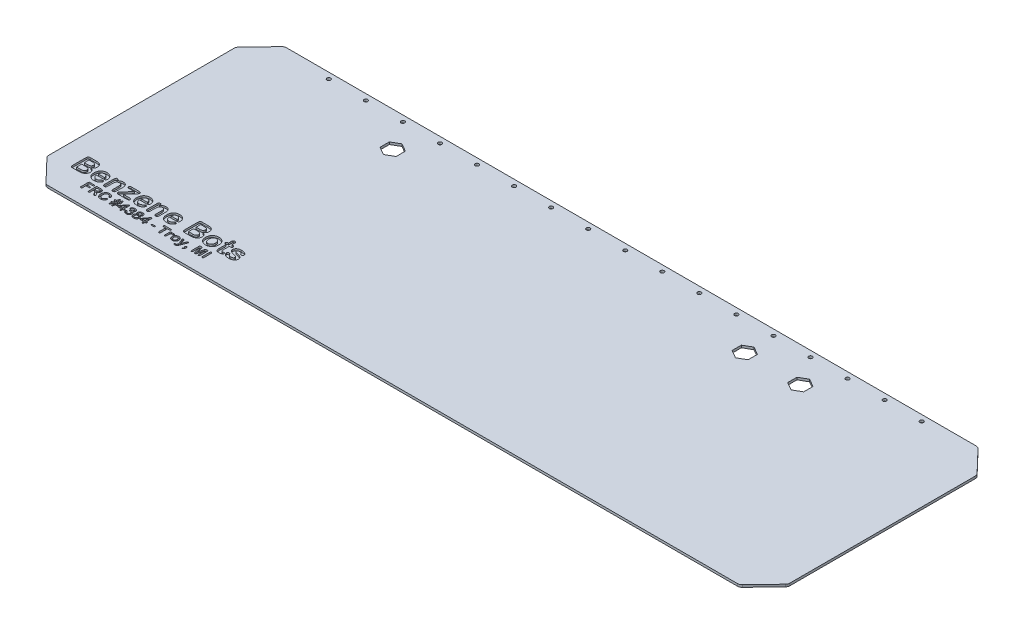
SolidWorks part; units mm, degrees
ref_plane "Front" through (0, 0, 0) normal (0, 0, 1) x (1, 0, 0)
ref_plane "Top" through (0, 0, 0) normal (0, 1, 0) x (1, 0, 0)
ref_plane "Right" through (0, 0, 0) normal (1, 0, 0) x (0, 0, -1)
sketch "Sketch1" plane through (0, 0, 0) normal (0, 1, 0) x (1, 0, 0)
  line L1 (6.35, 0) -> (1009.65, 0)
  line L2 (0, 6.35) -> (0, 320.675)
  line L3 (6.35, 327.025) -> (1009.65, 327.025)
  line L4 (1016, 6.35) -> (1016, 320.675)
  line L5 (0, 0) -> (1016, 327.025) construction
  line L6 (0, 327.025) -> (1016, 0) construction
  arc A0 (1009.65, 327.025) -> (1016, 320.675) centre (1009.65, 320.675) cw
  arc A1 (1009.65, 0) -> (1016, 6.35) centre (1009.65, 6.35) ccw
  arc A2 (6.35, 0) -> (0, 6.35) centre (6.35, 6.35) cw
  arc A3 (0, 320.675) -> (6.35, 327.025) centre (6.35, 320.675) cw
  point P4 (508, 163.5125)
  dimension "D1" = 327.025
  dimension "D2" = 1016
extrude "Base" add sketch "Sketch1" along normal blind 3.175
sketch "Sketch2" plane through (0, 3.175, 0) normal (0, 1, 0) x (1, 0, 0)
  line L0 (279.4, 327.025) -> (279.4, 0) construction
  line L1 (1009.65, 327.025) -> (6.35, 327.025) construction
  line L2 (6.35, 0) -> (1009.65, 0) construction
  line L3 (0, 320.675) -> (0, 6.35) construction
  line L4 (736.6, 327.025) -> (736.6, 0) construction
  line L5 (508, 318.77) -> (508, 327.025) construction
  circle A0 centre (508, 318.77) radius 2.54
  circle A1 centre (457.2, 318.77) radius 2.54
  circle A2 centre (406.4, 318.77) radius 2.54
  circle A3 centre (355.6, 318.77) radius 2.54
  circle A4 centre (304.8, 318.77) radius 2.54
  circle A5 centre (254, 318.77) radius 2.54
  circle A6 centre (203.2, 318.77) radius 2.54
  circle A7 centre (152.4, 318.77) radius 2.54
  circle A8 centre (558.8, 318.77) radius 2.54
  circle A9 centre (609.6, 318.77) radius 2.54
  circle A10 centre (660.4, 318.77) radius 2.54
  circle A11 centre (711.2, 318.77) radius 2.54
  circle A12 centre (762, 318.77) radius 2.54
  circle A13 centre (812.8, 318.77) radius 2.54
  circle A14 centre (863.6, 318.77) radius 2.54
  circle A15 centre (101.6, 318.77) radius 2.54
  circle A16 centre (914.4, 318.77) radius 2.54
  dimension "D3" = 8.255
  dimension "D4" = 5.08
  dimension "D1" = 279.4
  dimension "D2" = 736.6
  dimension "D7" = 50.8
  dimension "D8" = 50.8
  dimension "D5" = 9
  dimension "D6" = 9
extrude "Hinge Holes" cut sketch "Sketch2" against normal up to next
sketch "Sketch3" plane through (0, 3.175, 0) normal (0, 1, 0) x (1, 0, 0)
  line L0 (1.7649, 294.8705) -> (30.6983, 325.0681)
  line L1 (0, 320.675) -> (0, 6.35) construction
  line L2 (1009.65, 327.025) -> (6.35, 327.025) construction
  line L3 (508, 327.025) -> (508, 0) construction
  line L4 (6.35, 0) -> (1009.65, 0) construction
  line L5 (0, 163.5125) -> (1016, 163.5125) construction
  line L6 (1016, 6.35) -> (1016, 320.675) construction
  line L11 (1016, 290.4774) -> (1016, 327.025)
  line L12 (980.7167, 327.025) -> (1016, 327.025)
  line L13 (35.2833, 327.025) -> (0, 327.025)
  line L14 (0, 290.4774) -> (0, 327.025)
  line L25 (1014.2351, 294.8705) -> (985.3017, 325.0681)
  line L26 (1014.2351, 32.1545) -> (985.3017, 1.9569)
  line L27 (0, 36.5476) -> (0, 0)
  line L28 (35.2833, 0) -> (0, 0)
  line L29 (980.7167, 0) -> (1016, 0)
  line L30 (1016, 36.5476) -> (1016, 0)
  line L31 (1.7649, 32.1545) -> (30.6983, 1.9569)
  arc A3 (30.6983, 325.0681) -> (35.2833, 327.025) centre (35.2833, 320.675) cw
  arc A4 (1.7649, 294.8705) -> (0, 290.4774) centre (6.35, 290.4774) ccw
  arc A5 (1014.2351, 294.8705) -> (1016, 290.4774) centre (1009.65, 290.4774) cw
  arc A6 (985.3017, 325.0681) -> (980.7167, 327.025) centre (980.7167, 320.675) ccw
  arc A7 (985.3017, 1.9569) -> (980.7167, 0) centre (980.7167, 6.35) cw
  arc A8 (1014.2351, 32.1545) -> (1016, 36.5476) centre (1009.65, 36.5476) ccw
  arc A9 (1.7649, 32.1545) -> (0, 36.5476) centre (6.35, 36.5476) cw
  arc A10 (30.6983, 1.9569) -> (35.2833, 0) centre (35.2833, 6.35) ccw
  point P33 (35.2833, 327.025)
  point P36 (0, 290.4774)
  dimension "D1" = 6.35
  dimension "D2" = 50.8
extrude "Corner Cut" cut sketch "Sketch3" against normal up to next
sketch "Sketch4" plane through (0, 3.175, 0) normal (0, 1, 0) x (1, 0, 0)
  line L0 (279.4, 0) -> (279.4, 327.025) construction
  line L1 (35.2833, 0) -> (980.7167, 0) construction
  line L2 (980.7167, 327.025) -> (35.2833, 327.025) construction
  line L3 (736.6, 0) -> (736.6, 327.025) construction
  line L4 (0, 290.4774) -> (0, 36.5476) construction
  line L5 (260.35, 0) -> (260.35, 327.025) construction
  line L6 (755.65, 0) -> (755.65, 327.025) construction
  dimension "D1" = 279.4
  dimension "D2" = 736.6
  dimension "D3" = 19.05
  dimension "D4" = 19.05
sketch "Sketch5" plane through (0, 3.175, 0) normal (0, 1, 0) x (1, 0, 0)
  text T0 "Benzene Bots" font "Arial Rounded MT Bold" height 25.4
  text T1 "FRC #4384 - Troy, MI" font "Arial Rounded MT Bold" height 12.7
extrude "Text" cut sketch "Sketch5" against normal blind 2.54
sketch "Sketch6" plane through (0, 3.175, 0) normal (0, 1, 0) x (1, 0, 0)
  line L0 (508, 0) -> (508, 327.025) construction
  line L1 (228.6, 292.1) -> (217.6015, 285.75)
  line L2 (217.6015, 285.75) -> (217.6015, 273.05)
  line L3 (217.6015, 273.05) -> (228.6, 266.7)
  line L4 (228.6, 266.7) -> (239.5985, 273.05)
  line L5 (239.5985, 273.05) -> (239.5985, 285.75)
  line L6 (239.5985, 285.75) -> (228.6, 292.1)
  line L7 (35.2833, 0) -> (980.7167, 0) construction
  line L8 (980.7167, 327.025) -> (35.2833, 327.025) construction
  line L9 (776.4015, 285.75) -> (787.4, 292.1)
  line L10 (776.4015, 273.05) -> (776.4015, 285.75)
  line L11 (787.4, 266.7) -> (776.4015, 273.05)
  line L12 (798.3985, 273.05) -> (787.4, 266.7)
  line L13 (798.3985, 285.75) -> (798.3985, 273.05)
  line L14 (787.4, 292.1) -> (798.3985, 285.75)
  line L16 (700.2015, 273.05) -> (711.2, 266.7)
  line L17 (711.2, 266.7) -> (722.1985, 273.05)
  line L18 (722.1985, 273.05) -> (722.1985, 285.75)
  line L19 (722.1985, 285.75) -> (711.2, 292.1)
  line L20 (711.2, 292.1) -> (700.2015, 285.75)
  line L21 (700.2015, 285.75) -> (700.2015, 273.05)
  circle A0 centre (228.6, 279.4) radius 10.9985 construction
  circle A1 centre (787.4, 279.4) radius 10.9985 construction
  circle A2 centre (711.2, 279.4) radius 10.9985 construction
extrude "Cut-Extrude4" cut sketch "Sketch6" against normal up to next
